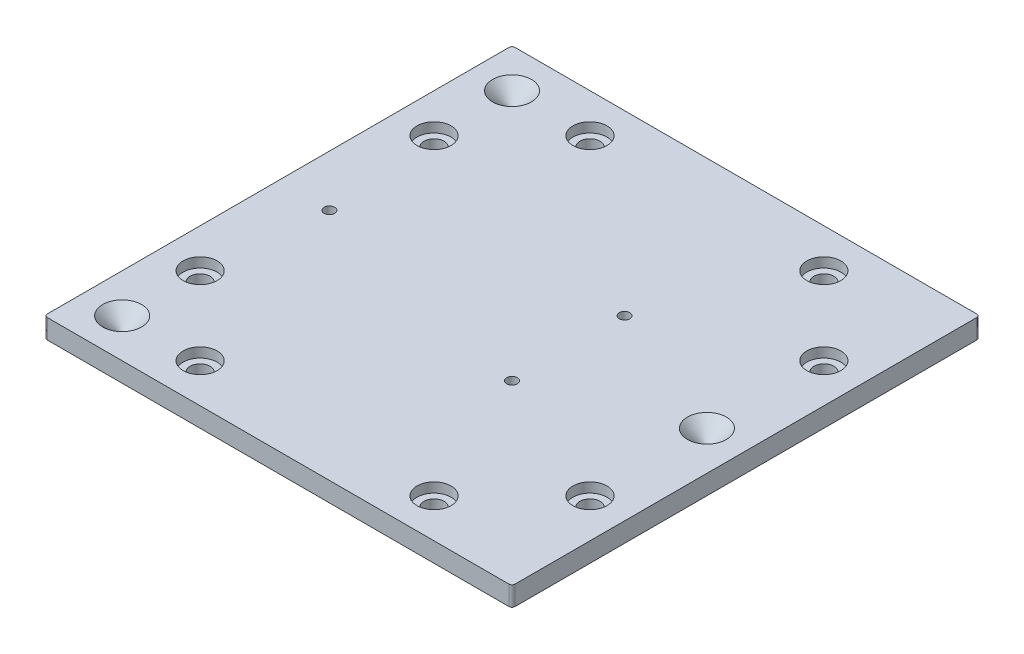
SolidWorks part; units mm, degrees
ref_plane "Front Plane" through (0, 0, 0) normal (0, 0, 1) x (1, 0, 0)
ref_plane "Top Plane" through (0, 0, 0) normal (0, 1, 0) x (1, 0, 0)
ref_plane "Right Plane" through (0, 0, 0) normal (1, 0, 0) x (0, 0, -1)
sketch "Sketch1" plane through (0, 0, 0) normal (0, 1, 0) x (1, 0, 0)
  line L0 (152.4, -76.2) -> (0, -76.2) construction
  line L1 (0, 0) -> (152.4, 0)
  line L2 (0, 0) -> (0, -152.4)
  line L3 (0, -152.4) -> (152.4, -152.4)
  line L4 (152.4, 0) -> (152.4, -152.4)
  line L5 (-6.35, 6.35) -> (158.75, 6.35) construction
  line L6 (-6.35, 6.35) -> (-6.35, -158.75) construction
  line L7 (-6.35, -158.75) -> (158.75, -158.75) construction
  line L8 (158.75, 6.35) -> (158.75, -158.75) construction
  circle A4 centre (12.7, -12.7) radius 3.2639
  circle A5 centre (139.7, -12.7) radius 3.2639
  circle A6 centre (139.7, -139.7) radius 3.2639
  circle A7 centre (12.7, -139.7) radius 3.2639
  circle A8 centre (38.1, -12.7) radius 3.2639
  circle A9 centre (114.3, -12.7) radius 3.2639
  circle A10 centre (139.7, -38.1) radius 3.2639
  circle A11 centre (139.7, -114.3) radius 3.2639
  circle A12 centre (114.3, -139.7) radius 3.2639
  circle A13 centre (38.1, -139.7) radius 3.2639
  circle A14 centre (12.7, -114.3) radius 3.2639
  circle A15 centre (12.7, -38.1) radius 3.2639
  point P5 (12.7, -12.7)
  point P6 (139.7, -12.7)
  point P7 (139.7, -139.7)
  point P8 (12.7, -139.7)
  point P40 (38.1, -12.7)
  point P41 (12.7, -38.1)
  point P42 (139.7, -38.1)
  point P43 (114.3, -12.7)
  point P44 (139.7, -114.3)
  point P45 (114.3, -139.7)
  point P46 (38.1, -139.7)
  point P47 (12.7, -114.3)
  dimension "D7" = 6.5278
  dimension "D1" = 127
  dimension "D2" = 127
  dimension "D3" = 12.7
  dimension "D4" = 12.7
  dimension "D5" = 12.7
  dimension "D6" = 12.7
  dimension "D8" = 165.1
  dimension "D10" = 6.35
  dimension "D11" = 152.4
  dimension "D12" = 6.35
  dimension "D13" = 38.1
  dimension "D15" = 38.1
  dimension "D14" = 38.1
  dimension "D16" = 38.1
extrude "Boss-Extrude1" add sketch "Sketch1" along normal blind 6.35 contours L4 L1 L2 L3 A15 A14 A13 A12 A11 A10 A9 A8 A7 A6 A5 A4 | A4 | A5 | A6 | A7 | A8 | A15 | A10 | A9 | A11 | A12 | A14 | A13 region at (76.2, 0, 76.2) region at (12.7, 0, 12.7) region at (139.7, 0, 12.7) region at (139.7, 0, 139.7) region at (12.7, 0, 139.7) region at (38.1, 0, 12.7) region at (114.3, 0, 12.7) region at (139.7, 0, 38.1) region at (139.7, 0, 114.3) region at (114.3, 0, 139.7) region at (38.1, 0, 139.7) region at (12.7, 0, 114.3) region at (12.7, 0, 38.1)
ref_plane "Top of Object Plane" through (0, 6.35, 0) normal (0, 1, 0) x (1, 0, 0)
ref_plane "Lower Object Plane" through (0, 0.508, 0) normal (0, 1, 0) x (1, 0, 0)
sketch "Sketch3" plane through (0, 6.35, 0) normal (0, 1, 0) x (1, 0, 0)
  line L0 (12.7, -6.358) -> (12.7, -19.042) construction
  line L1 (6.358, -12.7) -> (19.042, -12.7) construction
  line L2 (-6.35, 6.35) -> (-6.35, -158.75) construction
  line L3 (-6.35, 6.35) -> (158.75, 6.35) construction
  circle A0 centre (12.7, -12.7) radius 6.342
  dimension "D1" = 12.684
  dimension "D2" = 19.05
  dimension "D3" = 19.05
sketch "Sketch4" plane through (0, 0.508, 0) normal (0, 1, 0) x (1, 0, 0)
  line L0 (12.7, -12.2) -> (12.7, -13.2) construction
  line L1 (12.2, -12.7) -> (13.2, -12.7) construction
  circle A0 centre (12.7, -12.7) radius 0.5
  dimension "D1" = 1
loft "Cut-Loft1" cut profiles "Sketch3", "Sketch4" connector at (12.7, 6.35, 6.358) connector at (12.7, 0.508, 12.2)
sketch "Sketch5" plane through (0, 6.35, -6.35) normal (0, -1, 0) x (1, 0, 0)
  line L0 (12.7, 152.392) -> (12.7, 139.708) construction
  line L1 (6.358, 146.05) -> (19.042, 146.05) construction
  line L6 (-6.35, 165.1) -> (158.75, 165.1) construction
  line L7 (-6.35, 0) -> (-6.35, 165.1) construction
  circle A0 centre (12.7, 146.05) radius 6.342
  dimension "D2" = 19.05
  dimension "D3" = 19.05
  dimension "D1" = 12.684
sketch "Sketch6" plane through (0, 0.508, -1.35) normal (0, -1, 0) x (1, 0, 0)
  line L0 (12.7, 141.55) -> (12.7, 140.55) construction
  line L1 (12.2, 141.05) -> (13.2, 141.05) construction
  circle A0 centre (12.7, 141.05) radius 0.5
  dimension "D1" = 1
sketch "Sketch7" plane through (0, 6.35, 0) normal (0, 1, 0) x (1, 0, 0)
  line L0 (139.7, -69.858) -> (139.7, -82.542) construction
  line L1 (133.358, -76.2) -> (146.042, -76.2) construction
  line L3 (152.4, -76.2) -> (0, -76.2) construction
  line L4 (158.75, 6.35) -> (158.75, -158.75) construction
  circle A0 centre (139.7, -76.2) radius 6.342
  dimension "D2" = 19.05
  dimension "D1" = 12.684
sketch "Sketch8" plane through (0, 0.508, -1.35) normal (0, -1, 0) x (1, 0, 0)
  line L0 (139.7, 78.05) -> (139.7, 77.05) construction
  line L1 (139.2, 77.55) -> (140.2, 77.55) construction
  circle A0 centre (139.7, 77.55) radius 0.5
  dimension "D1" = 1
loft "Cut-Loft2" cut profiles "Sketch5", "Sketch6" connector at (7.1991, 6.35, 142.856) connector at (12.3462, 0.508, 140.0533)
loft "Cut-Loft4" cut profiles "Sketch7", "Sketch8" connector at (139.7, 6.35, 82.542) connector at (139.7, 0.508, 76.7)
hole_wizard "#8-32 Tapped Hole1" positions "3DSketch4" profile "Sketch9" tap size "#8-32" standard "ANSI Inch" end condition through all
sketch3d "3DSketch4"
  line L7 (-6.35, 0, -6.35) -> (-6.35, 0, 158.75) construction
  line L8 (158.75, 0, -6.35) -> (158.75, 0, 158.75) construction
  line L9 (-6.35, 0, -6.35) -> (158.75, 0, -6.35) construction
  line L10 (-6.35, 0, 158.75) -> (158.75, 0, 158.75) construction
  line L11 (152.4, 0, 76.2) -> (0, 0, 76.2) construction
  point P0 (16.7, 0, 76.2)
  point P4 (94.5382, 0, 57.8618)
  point P6 (94.5382, 0, 94.5382)
  dimension "D3" = 64.2118
  dimension "D1" = 23.05
  dimension "D2" = 64.2118
  dimension "D4" = 64.2118
  dimension "D5" = 64.2118
sketch "Sketch9" plane through (16.7, 0, 76.2) normal (1, 0, 0) x (0, 0, -1)
  line L0 (0, 0) -> (0, 6.3501)
  line L1 (0, 6.3501) -> (1.7272, 6.3501)
  line L2 (1.7272, 6.3501) -> (1.7272, 0)
  line L5 (1.7272, 0) -> (0, 0)
  line L11 (0, -6.35) -> (0, 107.95) construction
  dimension "Thru Tap Drill Dia." = 3.4544
  dimension "Thru Tap Drill Depth" = 6.3501
cosmetic thread "Hole Thread3" parameters "D2"=4.1656
cosmetic thread "Hole Thread4" parameters "D2"=4.1656
cosmetic thread "Hole Thread5" parameters "D2"=4.1656
hole_wizard "CBORE for 1/4 Socket Head Cap Screw1" positions "3DSketch5" profile "Sketch10" counterbore size "1/4" standard "ANSI Inch" end condition through all
sketch3d "3DSketch5"
  point P0 (38.1, 6.35, 12.7)
  point P2 (12.7, 6.35, 38.1)
  point P4 (114.3, 6.35, 12.7)
  point P6 (139.7, 6.35, 38.1)
  point P8 (139.7, 6.35, 114.3)
  point P10 (114.3, 6.35, 139.7)
  point P12 (38.1, 6.35, 139.7)
  point P14 (12.7, 6.35, 114.3)
sketch "Sketch10" plane through (38.1, 6.35, 12.7) normal (1, 0, 0) x (0, 0, 1)
  line L0 (0, 0) -> (0, 6.35)
  line L1 (0, 6.35) -> (3.2639, 6.35)
  line L3 (3.2639, 6.35) -> (3.2639, 3.175)
  line L4 (3.2639, 3.175) -> (5.5562, 3.175)
  line L5 (5.5562, 3.175) -> (5.5562, 0)
  line L7 (5.5562, 0) -> (0, 0)
  line L11 (0, -6.35) -> (0, 107.95) construction
  dimension "Thru Hole Dia." = 6.5278
  dimension "Thru Hole Depth" = 6.35
  dimension "C'Bore Dia." = 11.1125
  dimension "C'Bore Depth" = 3.175
fillet "Fillet1" radius 1 4 edges at (152.4, 3.175, 152.4) (152.4, 3.175, 0) (0, 3.175, 0) (0, 3.175, 152.4)
equation "\"D2@Sketch1\"=\"D1@Sketch1\""
equation "\"D4@Sketch1\"=\"D3@Sketch1\""
equation "\"D5@Sketch1\"=\"D3@Sketch1\""
equation "\"D6@Sketch1\"=\"D5@Sketch1\""
equation "\"D9@Sketch1\"=\"D8@Sketch1\""
equation "\"D12@Sketch1\"=\"D10@Sketch1\""
equation "\"D3@Sketch3\"=\"D2@Sketch3\""
equation "\"Ball_rest_location\"= 12.7 + 6.35"
equation "\"D2@Sketch3\"=\"Ball_rest_location\""
equation "\"D2@Sketch5\"=\"Ball_rest_location\""
equation "\"D3@Sketch5\"=\"D2@Sketch5\""
equation "\"D15@Sketch1\"=\"D13@Sketch1\""
equation "\"D14@Sketch1\"=\"D13@Sketch1\""
equation "\"D16@Sketch1\"=\"D13@Sketch1\""
equation "\"D2@Sketch7\"=\"Ball_rest_location\""
equation "\"D3@3DSketch4\"=\"D2@3DSketch4\""
equation "\"D4@3DSketch4\"=\"D3@3DSketch4\""
equation "\"D5@3DSketch4\"=\"D4@3DSketch4\""
equation "\"Outer_circle_Dia\"= 12.6840mm"
equation "\"D1@Sketch3\"=\"Outer_circle_Dia\""
equation "\"D1@Sketch5\"=\"Outer_circle_Dia\""
equation "\"D1@Sketch7\"=\"Outer_circle_Dia\""
